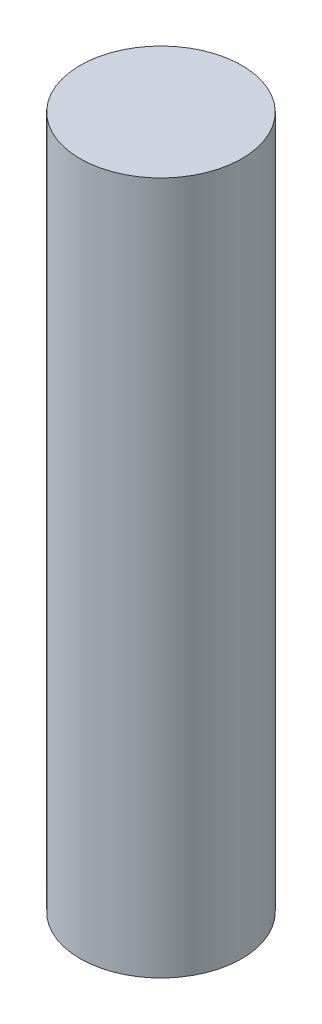
SolidWorks part; units mm, degrees
ref_plane "Спереди" through (0, 0, 0) normal (0, 0, 1) x (1, 0, 0)
ref_plane "Сверху" through (0, 0, 0) normal (0, 1, 0) x (1, 0, 0)
ref_plane "Справа" through (0, 0, 0) normal (1, 0, 0) x (0, 0, -1)
sketch "Эскиз1" plane through (0, 0, 0) normal (0, 0, 1) x (1, 0, 0)
  line L5 (-30, 50) -> (0, 50)
  line L6 (0, 0) -> (-35, 0)
  line L7 (-35, 0) -> (-35, 300)
  line L8 (-35, 300) -> (0, 300)
  line L10 (0, 300) -> (0, 280)
  line L11 (0, 280) -> (-30, 280)
  line L12 (-30, 280) -> (-30, 50)
  line L13 (0, 50) -> (0, 0)
  dimension "D1" = 50
  dimension "D2" = 20
  dimension "D3" = 35
  dimension "D4" = 300
  dimension "D5" = 5
revolve "Повернуть1" add sketch "Эскиз1" angle 360 about L13
ref_plane "Плоскость4" through (0, 0, -32) normal (0, 0, 1) x (1, 0, 0)
sketch "Эскиз2" plane through (0, 0, -32) normal (0, 0, 1) x (1, 0, 0)
  line L0 (0, 0) -> (0, 300) construction
  line L1 (35, 300) -> (-35, 300) construction
  circle A0 centre (0, 25) radius 10
  point P7 (0, 0)
  dimension "D1" = 20
  dimension "D2" = 25
extrude "Вырез-Вытянуть1" cut sketch "Эскиз2" against normal blind 10 and the other way blind 10
